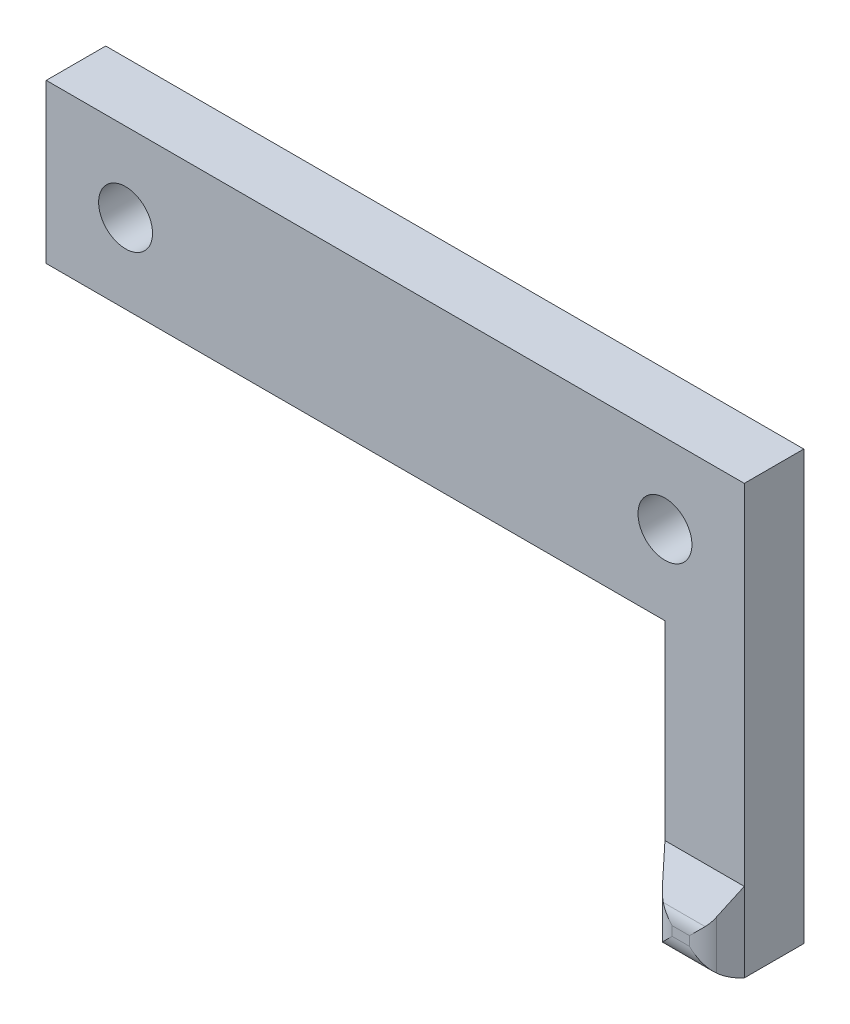
SolidWorks part; units mm, degrees
ref_plane "Front Plane" through (0, 0, 0) normal (0, 0, 1) x (1, 0, 0)
ref_plane "Top Plane" through (0, 0, 0) normal (0, 1, 0) x (1, 0, 0)
ref_plane "Right Plane" through (0, 0, 0) normal (1, 0, 0) x (0, 0, -1)
sketch "Sketch1" plane through (0, 0, 0) normal (0, 0, 1) x (1, 0, 0)
  line L0 (0, 0) -> (68, 0) construction
  line L2 (78, 10) -> (-10, 10)
  line L3 (78, 10) -> (78, -10)
  line L4 (78, -10) -> (-10, -10)
  line L5 (-10, 10) -> (-10, -10)
  line L6 (78, 10) -> (-10, -10) construction
  line L7 (78, -10) -> (-10, 10) construction
  circle A0 centre (0, 0) radius 3.4
  circle A1 centre (68, 0) radius 3.4
  point P5 (34, 0)
  dimension "D2" = 6.8
  dimension "D3" = 10
  dimension "D1" = 68
  dimension "D4" = 10
extrude "Boss-Extrude1" add sketch "Sketch1" along normal blind 7.5
sketch "Sketch2" plane through (0, -10, 0) normal (0, -1, 0) x (1, 0, 0)
  line L0 (68, 0) -> (78, 0)
  line L1 (78, 0) -> (78, 7.5)
  line L2 (-10, 7.5) -> (78, 7.5) construction
  line L3 (78, 7.5) -> (68, 7.5)
  line L4 (68, 7.5) -> (68, 0)
  line L5 (78, 7.5) -> (78, 0) construction
  dimension "D1" = 10
extrude "Boss-Extrude2" add sketch "Sketch2" along normal blind 34
ref_plane "Plane1" through (0, 0, 10.5) normal (0, 0, 1) x (1, 0, 0)
sketch "Sketch3" plane through (0, 0, 10.5) normal (0, 0, 1) x (1, 0, 0)
  line L0 (78, -44) -> (68, -34) construction
  line L2 (68, -34) -> (68, -44) construction
  line L3 (73, -39) -> (73, -44) construction
  line L4 (75.5, -39) -> (70.5, -39)
  line L5 (75.5, -39) -> (75.5, -44)
  line L6 (75.5, -44) -> (70.5, -44)
  line L7 (70.5, -39) -> (70.5, -44)
  line L8 (75.5, -39) -> (70.5, -44) construction
  line L9 (75.5, -44) -> (70.5, -39) construction
  line L10 (78, -44) -> (68, -44) construction
  point P5 (73, -41.5)
  point P13 (73, -39)
  dimension "D1" = 10
  dimension "D2" = 5
sketch "Sketch4" plane through (0, 0, 7.5) normal (0, 0, 1) x (1, 0, 0)
  line L0 (68, -34) -> (78, -44) construction
  line L2 (78, -44) -> (68, -44)
  line L3 (78, -44) -> (78, -34)
  line L4 (78, -34) -> (68, -34)
  line L5 (68, -44) -> (68, -34)
  dimension "D1" = 10
loft "Loft1" add profiles "Sketch4", "Sketch3"
fillet "Fillet1" radius 3 4 edges
